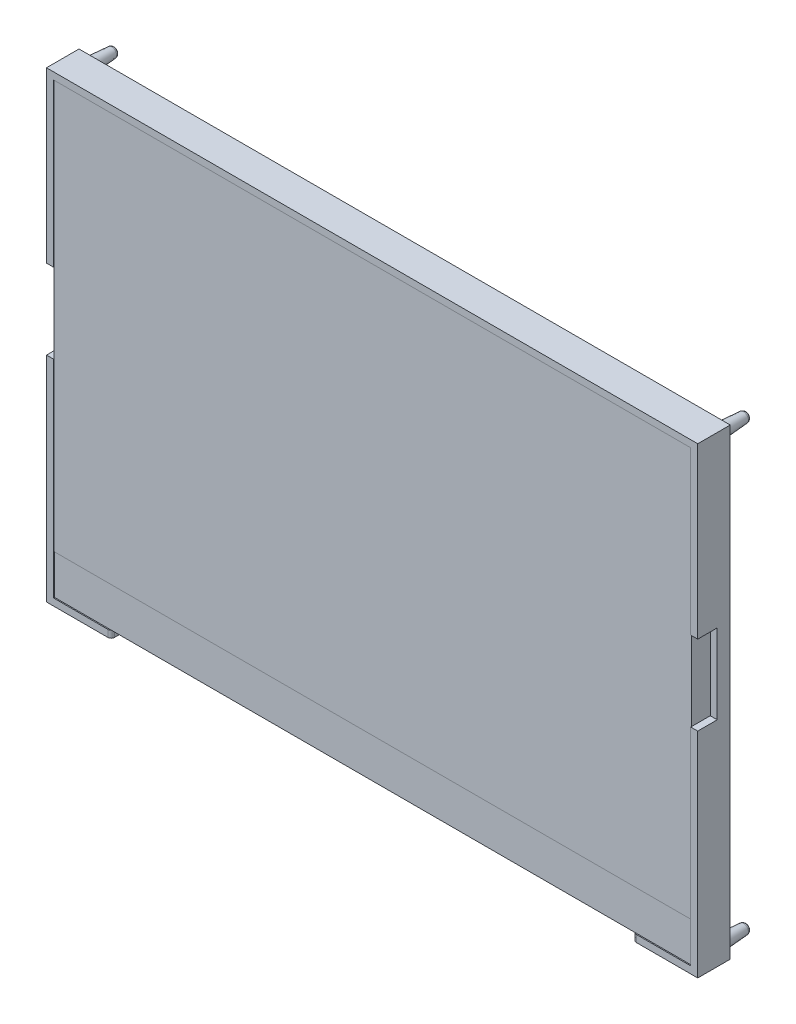
SolidWorks part; units mm, degrees
ref_plane "Plan de face" through (0, 0, 0) normal (0, 0, 1) x (1, 0, 0)
ref_plane "Plan de dessus" through (0, 0, 0) normal (0, 1, 0) x (1, 0, 0)
ref_plane "Plan de droite" through (0, 0, 0) normal (1, 0, 0) x (0, 0, -1)
sketch "Esquisse2" plane through (0, 0, 0) normal (0, 0, 1) x (1, 0, 0)
  line L1 (-50.075, -35.575) -> (50.075, -35.575)
  line L2 (-50.075, -35.575) -> (-50.075, 35.575)
  line L3 (-50.075, 35.575) -> (50.075, 35.575)
  line L4 (50.075, -35.575) -> (50.075, 35.575)
  line L5 (-50.075, -35.575) -> (50.075, 35.575) construction
  line L6 (-50.075, 35.575) -> (50.075, -35.575) construction
  point P0 (0, 0)
  dimension "D1" = 100.15
  dimension "D2" = 71.15
extrude "Boss.-Extru.1" add sketch "Esquisse2" along normal blind 5
sketch "Esquisse3" plane through (0, 0, 5) normal (0, 0, 1) x (1, 0, 0)
  line L1 (-49, -34.5) -> (49, -34.5)
  line L2 (-49, -34.5) -> (-49, 34.5)
  line L3 (-49, 34.5) -> (49, 34.5)
  line L4 (49, -34.5) -> (49, 34.5)
  line L5 (-49, -34.5) -> (49, 34.5) construction
  line L6 (-49, 34.5) -> (49, -34.5) construction
  point P0 (0, 0)
  dimension "D1" = 98
  dimension "D2" = 69
extrude "Enlèv. mat.-Extru.1" cut sketch "Esquisse3" against normal blind 0.08
sketch "Esquisse4" plane through (0, 0, 4.92) normal (0, 0, 1) x (1, 0, 0)
  line L0 (49, -34.5) -> (49, 34.5) construction
  line L1 (-49, -34.5) -> (49, -34.5)
  line L2 (-49, -34.5) -> (-49, -28.3591)
  line L3 (-49, -28.3591) -> (49, -28.3591)
  line L4 (49, -34.5) -> (49, -28.3591)
extrude "Enlèv. mat.-Extru.2" cut sketch "Esquisse4" against normal blind 0.08
sketch "Esquisse5" plane through (0, 0, 5) normal (0, 0, 1) x (1, 0, 0)
  line L0 (-50.075, -35.575) -> (-40.125, -35.575) construction
  line L1 (-50.075, -35.575) -> (50.075, -35.575) construction
  line L2 (50.075, -35.575) -> (40.1247, -35.575) construction
  line L3 (-49, -34.5) -> (49, -34.5) construction
  line L4 (40.1247, -35.575) -> (-40.125, -35.575)
  line L5 (40.1247, -35.575) -> (40.1247, -34.5)
  line L6 (40.1247, -34.5) -> (-40.125, -34.5)
  line L7 (-40.125, -35.575) -> (-40.125, -34.5)
  dimension "D1" = 9.95
extrude "Enlèv. mat.-Extru.3" cut sketch "Esquisse5" against normal blind 3
fillet "Congé1" radius 0.5 1 edges at (-40.125, -35.0375, 5)
fillet "Congé2" radius 0.5 1 edges at (40.1247, -35.0375, 5)
sketch "Esquisse7" plane through (0, 0, 5) normal (0, 0, 1) x (1, 0, 0)
  line L0 (-50.075, -35.575) -> (-50.075, -2.6885) construction
  line L1 (-50.075, 35.575) -> (-50.075, -35.575) construction
  line L2 (-50.075, 35.575) -> (-50.075, 9.5547) construction
  line L3 (-49, 34.5) -> (-49, -34.5) construction
  line L4 (-50.075, 9.5547) -> (-49, 9.5547)
  line L5 (-50.075, 9.5547) -> (-50.075, -2.6885)
  line L6 (-50.075, -2.6885) -> (-49, -2.6885)
  line L7 (-49, 9.5547) -> (-49, -2.6885)
  line L8 (49, -34.5) -> (49, 34.5) construction
  line L9 (49, 9.5547) -> (50.075, 9.5547)
  line L10 (49, 9.5547) -> (49, -2.6885)
  line L11 (49, -2.6885) -> (50.075, -2.6885)
  line L12 (50.075, 9.5547) -> (50.075, -2.6885)
  line L13 (50.075, -35.575) -> (50.075, 35.575) construction
extrude "Enlèv. mat.-Extru.4" cut sketch "Esquisse7" against normal blind 3
sketch "Esquisse8" plane through (0, 0, 0) normal (0, 0, -1) x (-1, 0, 0)
  line L0 (-50.075, 35.575) -> (-48.5774, 35.575) construction
  line L1 (-50.075, 35.575) -> (50.075, 35.575) construction
  line L2 (-48.5774, 35.575) -> (-48.5774, 34.0759) construction
  line L3 (-48.5774, 34.0759) -> (50.075, 34.0759) construction
  line L4 (50.075, 35.575) -> (50.075, -35.575) construction
  line L5 (50.075, 34.0759) -> (48.5782, 34.0759) construction
  line L6 (48.5782, 34.0759) -> (48.5782, -35.575) construction
  line L7 (50.075, -35.575) -> (-50.075, -35.575) construction
  line L8 (48.5782, -35.575) -> (48.5782, -34.075) construction
  line L9 (48.5782, -34.075) -> (-50.075, -34.075) construction
  line L10 (-50.075, -35.575) -> (-50.075, 35.575) construction
  line L11 (-50.075, -34.075) -> (-48.5774, -34.075) construction
  circle A0 centre (-48.5774, -34.075) radius 1
  circle A1 centre (-48.5774, 34.0759) radius 1
  circle A2 centre (48.5782, 34.0759) radius 1
  circle A3 centre (48.5782, -34.075) radius 1
extrude "Boss.-Extru.3" add sketch "Esquisse8" along normal blind 4 draft 4
fillet "Congé3" radius 0.5 1 edges at (47.8571, 34.0759, -4)
fillet "Congé4" radius 0.5 1 edges at (-49.2985, 34.0759, -4)
fillet "Congé5" radius 0.5 1 edges at (-49.2985, -34.075, -4)
fillet "Congé6" radius 0.5 1 edges at (47.8571, -34.075, -4)
sketch "Esquisse9" plane through (0, 0, 0) normal (0, 0, -1) x (-1, 0, 0)
  line L0 (0, -35.575) -> (-26.5, -35.575) construction
  line L1 (50.075, -35.575) -> (-50.075, -35.575) construction
  line L2 (0, -35.575) -> (26.5, -35.575) construction
  line L3 (-26.5, -35.575) -> (-26.5, -34.4762) construction
  line L4 (0, -35.575) -> (0, -34.4762) construction
  line L5 (26.5, -35.575) -> (26.5, -34.4762) construction
  circle A0 centre (26.5, -34.4762) radius 0.15
  circle A1 centre (-26.5, -34.4762) radius 0.15
  dimension "D1" = 26.5
  dimension "D2" = 26.5
extrude "Boss.-Extru.5" add sketch "Esquisse9" along normal blind 4
